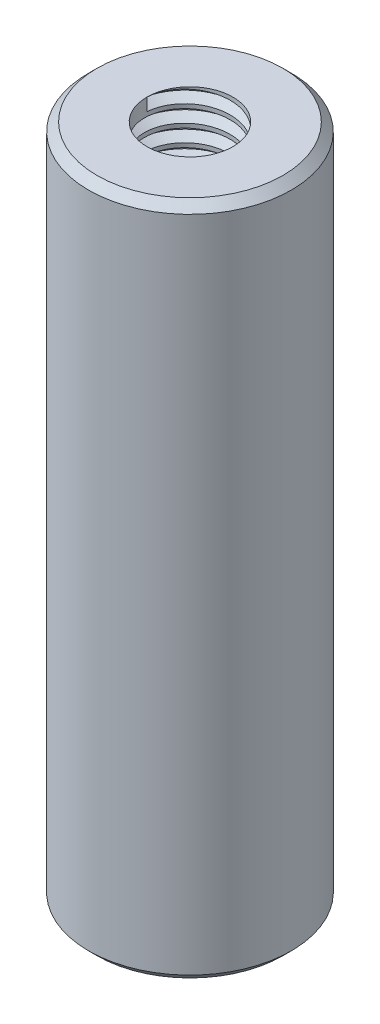
SolidWorks part; units mm, degrees
material "6061-T6 (SS)"
ref_plane "Alzado" through (0, 0, 0) normal (0, 0, 1) x (1, 0, 0)
ref_plane "Planta" through (0, 0, 0) normal (0, 1, 0) x (1, 0, 0)
ref_plane "Vista lateral" through (0, 0, 0) normal (1, 0, 0) x (0, 0, -1)
sketch "Croquis2" plane through (0, 0, 0) normal (0, 1, 0) x (1, 0, 0)
  circle A0 centre (0, 0) radius 4.7625
  dimension "D1" = 9.525
extrude "Saliente-Extruir1" add sketch "Croquis2" along normal mid plane 31.75
chamfer "Chaflán1" distance 0.3969 angle 45 2 edges at (0, -15.875, 4.7625) (0, 15.875, 4.7625)
sketch "Croquis3" plane through (0, 0, 0) normal (0, 1, 0) x (1, 0, 0)
  circle A0 centre (0, 0) radius 2.0193
  dimension "D1" = 4.0386
extrude "Tap Hole 1" cut sketch "Croquis3" against normal blind 12.7 from surface starting at face at (0, 15.875, 4.3656)
extrude "Tap Hole 2" cut sketch "Croquis3<2>" along normal blind 12.7 from surface starting at face at (0, -15.875, 4.3656)
sketch "Croquis3<2>" plane through (0, 0, 0) normal (0, 1, 0) x (1, 0, 0) same geometry as "Croquis3"
sketch "Croquis4" plane through (0, 0, 0) normal (0, 1, 0) x (1, 0, 0)
  circle A0 centre (0, 0) radius 2.4892
  dimension "D1" = 4.9784
extrude "Clearance Hole" [suppressed] cut sketch "Croquis4" against normal through all both and the other way through all
thread "Rosca1" pitch 0.7937 method cut profile "Perfil de rosca2" start angle 0, offset 0, length 0, pitch 0.7937, diameter 4.0386
ref_plane "Plano2" through (-2.0193, 15.875, 0) normal (0, 0, 1) x (-1, 0, 0)
sketch "Perfil de rosca2" plane through (-2.0193, 15.875, 0) normal (0, 0, 1) x (-1, 0, 0)
  line L0 (0, 0) -> (0, 0.7937) construction
  line L1 (0, 0) -> (0.4296, 0.248)
  line L2 (0.4296, 0.248) -> (0.4296, 0.3473)
  line L3 (0.4296, 0.3473) -> (0, 0.5953)
  line L4 (0.4296, 0.2977) -> (0, 0.2977) construction
  line L11 (0, 0) -> (0, 0.5953)
  point P2 (0, 0)
  dimension "Pitch" = 0.7937
  dimension "Profile_Angle" = 60
  dimension "Profile_Land" = 0.0992
  dimension "Profile_Height" = 0.4296
thread "Rosca2" pitch 0.7937 method cut profile "Perfil de rosca3" start angle 0, offset 0, length 0, pitch 0.7937, diameter 4.0386
ref_plane "Plano3" through (2.0193, -15.875, 0) normal (0, 0, 1) x (1, 0, 0)
sketch "Perfil de rosca3" plane through (2.0193, -15.875, 0) normal (0, 0, 1) x (1, 0, 0)
  line L0 (0, 0) -> (0, 0.7937) construction
  line L1 (0, 0) -> (0.4296, 0.248)
  line L2 (0.4296, 0.248) -> (0.4296, 0.3473)
  line L3 (0.4296, 0.3473) -> (0, 0.5953)
  line L4 (0.4296, 0.2977) -> (0, 0.2977) construction
  line L11 (0, 0) -> (0, 0.5953)
  point P2 (0, 0)
  dimension "Pitch" = 0.7937
  dimension "Profile_Angle" = 60
  dimension "Profile_Land" = 0.0992
  dimension "Profile_Height" = 0.4296
equation "\"OD\" = 0.375pulgadas"
equation "\"Largo\"= 1.25pulgadas"
equation "\"Tap Hole\"= IIF ( \"OD\" = 0.375pulgadas , 0.1590pulgadas , 0.201pulgadas )"
equation "\"Spacer Hole\"= IIF ( \"OD\" = 0.375pulgadas , 0.196pulgadas , 0.257pulgadas )"
equation "\"D1@Croquis2\"=\"OD\""
equation "\"D1@Saliente-Extruir1\"=\"Largo\""
equation "\"D1@Croquis3\"=\"Tap Hole\""
equation "\"D1@Croquis4\"=\"Spacer Hole\""
